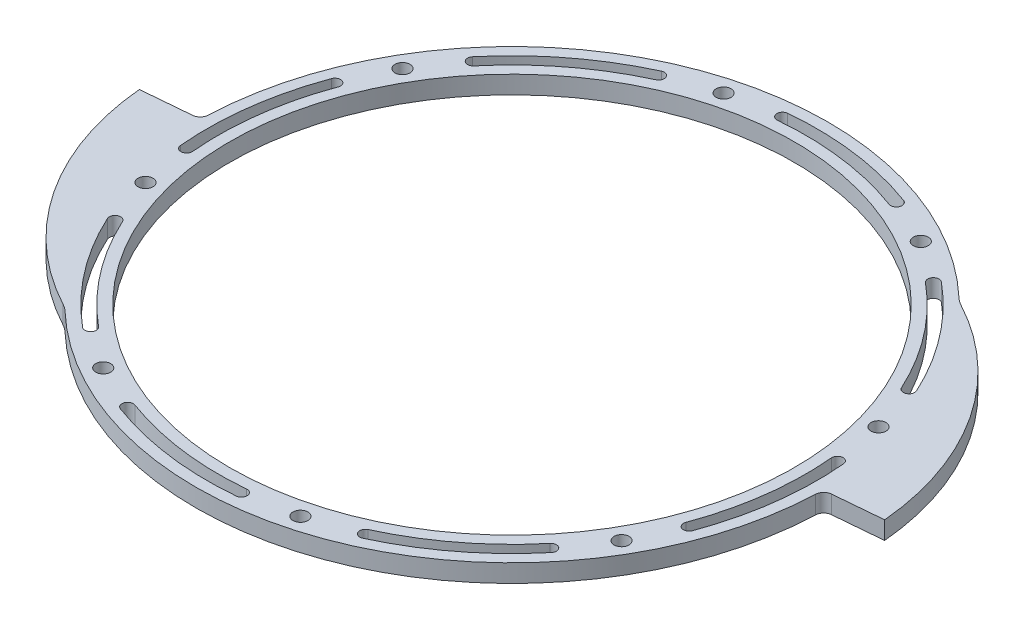
SolidWorks part; units mm, degrees
material "Alloy Steel"
ref_plane "Front Plane" through (0, 0, 0) normal (0, 0, 1) x (1, 0, 0)
ref_plane "Top Plane" through (0, 0, 0) normal (0, 1, 0) x (1, 0, 0)
ref_plane "Right Plane" through (0, 0, 0) normal (1, 0, 0) x (0, 0, -1)
sketch "Sketch1" plane through (0, 0, 0) normal (0, 1, 0) x (1, 0, 0)
  line L0 (0, 0) -> (-132, 0) construction
  line L1 (-132.0082, 0.0941) -> (-134.7743, 31.7103) construction
  line L2 (-111.9863, 1.751) -> (-132, 0)
  line L3 (-132, 0) -> (-132, 32.0934) construction
  line L4 (-129.3938, 0) -> (-182.8754, 0) construction
  line L5 (-112, 0) -> (-132, 0) construction
  line L6 (-79.4774, -79.4774) -> (0, 0) construction
  circle A0 centre (0, 0) radius 100
  arc A10 (-132, 0) -> (-79.4774, -79.4774) centre (-32.4231, 8.7118) ccw
  arc A11 (-79.4774, -79.4774) -> (-77.2845, -81.0624) centre (-84.1849, -88.3001) cw
  arc A12 (-77.2845, -81.0624) -> (-111.9863, 1.751) centre (0, 0) ccw
  dimension "D1" = 200
  dimension "D6" = 10
  dimension "D4" = 5
  dimension "D7" = 45
  dimension "D2" = 12
  dimension "D3" = 5
  dimension "D5" = 20
extrude "Boss-Extrude1" add sketch "Sketch1" along normal mid plane 6.35
fillet "Fillet1" radius 3 1 edges at (-111.9863, 0, -1.751)
pattern_circular "CirPattern1" count 2 over 360 about axis through (0, 3.175, 0) along (0, -1, 0) of "Boss-Extrude1", "Fillet1" reverse direction yes
sketch "Sketch2" plane through (0, 3.175, 0) normal (0, 1, 0) x (1, 0, 0)
  line L0 (-102.3881, -27.4348) -> (0, 0) construction
  line L1 (0, 0) -> (-106, 0) construction
  circle A0 centre (-102.3881, -27.4348) radius 2.65
  circle A2 centre (0, 0) radius 106 construction
  circle A3 centre (0, 0) radius 100 construction
  dimension "D3" = 5.3
  dimension "D1" = 106
  dimension "D2" = 6
  dimension "D4" = 15
extrude "Cut-Extrude1" cut sketch "Sketch2" against normal through all
pattern_circular "CirPattern2" count 8 over 360 about axis through (0, 3.175, 0) along (0, -1, 0) of "Cut-Extrude1"
sketch "Sketch3" plane through (0, 3.175, 0) normal (0, 1, 0) x (1, 0, 0)
  line L0 (-102.3881, -27.4348) -> (0, 0) construction
  line L1 (-102.3881, -27.4348) -> (0, 0) construction
  line L2 (0, 0) -> (-91.7987, 53) construction
  line L3 (-105.0932, 13.8358) -> (0, 0) construction
  arc A0 (-105.5538, -9.7154) -> (-99.4426, 36.7037) centre (0, 0) cw construction
  circle A1 centre (0, 0) radius 106 construction
  arc A2 (-101.3189, 37.3962) -> (-107.5454, -9.8987) centre (0, 0) ccw
  arc A3 (-97.5664, 36.0112) -> (-103.5622, -9.5321) centre (0, 0) ccw
  arc A4 (-97.5664, 36.0112) -> (-101.3189, 37.3962) centre (-99.4426, 36.7037) ccw
  arc A5 (-107.5454, -9.8987) -> (-103.5622, -9.5321) centre (-105.5538, -9.7154) ccw
  point P3 (-105.0932, 13.8358)
  point P12 (-106.9513, 14.0804)
  dimension "D4" = 2
  dimension "D1" = 45
  dimension "D2" = 22.5
  dimension "D3" = 18
extrude "Lightening Cut" cut sketch "Sketch3" against normal through all
pattern_circular "Lightening Pattern" count 8 over 360 about axis through (0, 3.175, 0) along (0, -1, 0) of "Lightening Cut"
equation "\"ring_id\"=200"
equation "\"D1@Sketch1\"=\"ring_id\""
equation "\"D2@Sketch2\"=\"D2@Sketch1\"/2"
equation "\"D2@Sketch3\"=\"D1@Sketch3\"/2"
